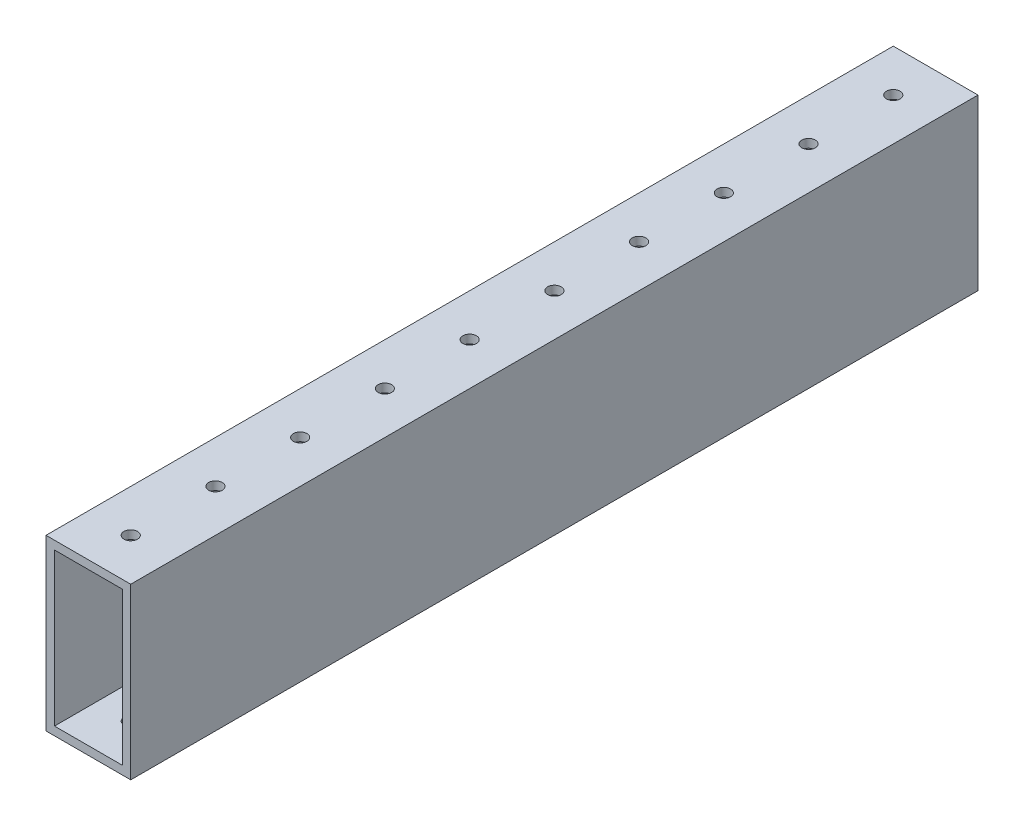
SolidWorks part; units mm, degrees
ref_plane "Front Plane" through (0, 0, 0) normal (0, 0, 1) x (1, 0, 0)
ref_plane "Top Plane" through (0, 0, 0) normal (0, 1, 0) x (1, 0, 0)
ref_plane "Right Plane" through (0, 0, 0) normal (1, 0, 0) x (0, 0, -1)
sketch "Sketch1" plane through (0, 0, 0) normal (0, 0, 1) x (1, 0, 0)
  line L0 (-10.16, 22.86) -> (10.16, 22.86)
  line L1 (-12.7, 25.4) -> (12.7, 25.4)
  line L2 (-12.7, 25.4) -> (-12.7, -25.4)
  line L3 (-12.7, -25.4) -> (12.7, -25.4)
  line L4 (12.7, 25.4) -> (12.7, -25.4)
  line L5 (-12.7, 25.4) -> (12.7, -25.4) construction
  line L6 (-12.7, -25.4) -> (12.7, 25.4) construction
  line L7 (10.16, 22.86) -> (10.16, -22.86)
  line L8 (-10.16, -22.86) -> (10.16, -22.86)
  line L9 (-10.16, 22.86) -> (-10.16, -22.86)
  point P0 (0, 0)
  dimension "D1" = 50.8
  dimension "D2" = 25.4
  dimension "D3" = 2.54
extrude "Boss-Extrude1" add sketch "Sketch1" against normal blind 254
sketch "Sketch2" plane through (0, 25.4, 0) normal (0, 1, 0) x (1, 0, 0)
  line L0 (0, -1000) -> (0, 49000) construction
  line L1 (12.7, 0) -> (-12.7, 0) construction
  line L2 (0, 12.7) -> (0, 38.1) construction
  circle A0 centre (0, 12.7) radius 2.032
  circle A1 centre (0, 38.1) radius 2.032
  circle A2 centre (0, 63.5) radius 2.032
  circle A3 centre (0, 88.9) radius 2.032
  circle A4 centre (0, 114.3) radius 2.032
  circle A5 centre (0, 139.7) radius 2.032
  circle A6 centre (0, 165.1) radius 2.032
  circle A7 centre (0, 190.5) radius 2.032
  circle A8 centre (0, 215.9) radius 2.032
  circle A9 centre (0, 241.3) radius 2.032
  circle A10 centre (0, 266.7) radius 2.032
  circle A11 centre (0, 292.1) radius 2.032
  circle A12 centre (0, 317.5) radius 2.032
  circle A13 centre (0, 342.9) radius 2.032
  circle A14 centre (0, 368.3) radius 2.032
  circle A15 centre (0, 393.7) radius 2.032
  circle A16 centre (0, 419.1) radius 2.032
  circle A17 centre (0, 444.5) radius 2.032
  circle A18 centre (0, 469.9) radius 2.032
  circle A19 centre (0, 495.3) radius 2.032
  circle A20 centre (0, 520.7) radius 2.032
  circle A21 centre (0, 546.1) radius 2.032
  circle A22 centre (0, 571.5) radius 2.032
  circle A23 centre (0, 596.9) radius 2.032
  circle A24 centre (0, 622.3) radius 2.032
  circle A25 centre (0, 647.7) radius 2.032
  circle A26 centre (0, 673.1) radius 2.032
  circle A27 centre (0, 698.5) radius 2.032
  circle A28 centre (0, 723.9) radius 2.032
  circle A29 centre (0, 749.3) radius 2.032
  dimension "D1" = 4.064
  dimension "D2" = 12.7
  dimension "D4" = 25.4
  dimension "D3" = 30
extrude "Cut-Extrude1" cut sketch "Sketch2" against normal through all
